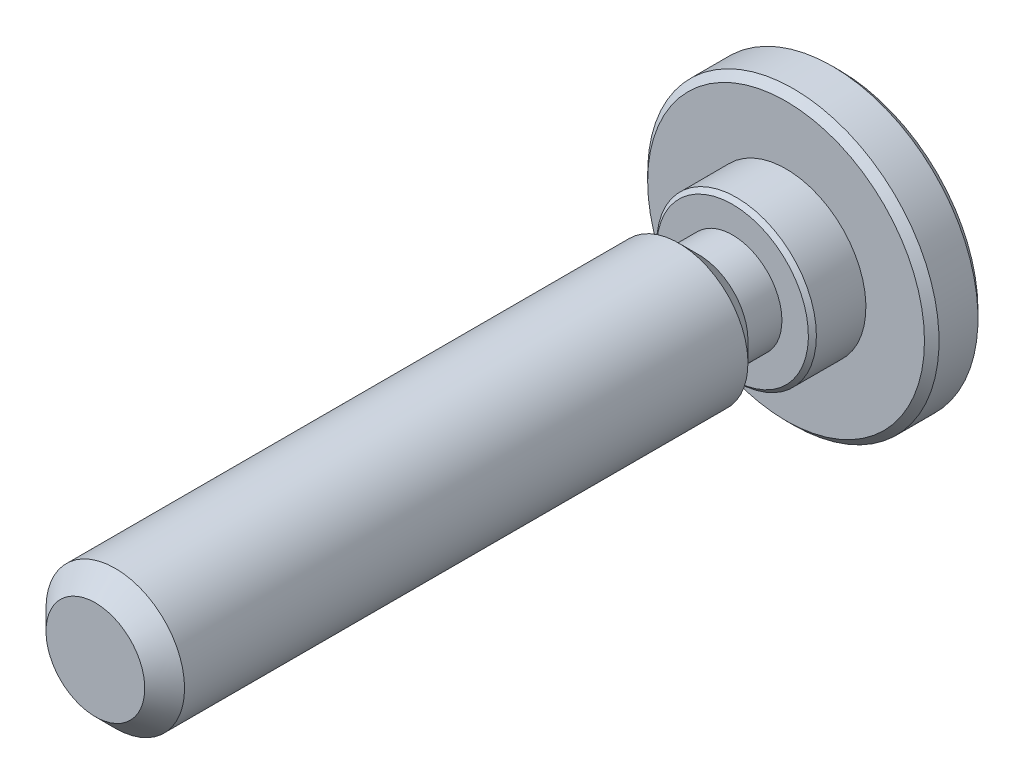
SolidWorks part; units mm, degrees
other "DetailItem1"
material "Stainless Steel (ferritic)"
ref_plane "Front Plane" through (0, 0, 0) normal (0, 0, 1) x (1, 0, 0)
ref_plane "Top Plane" through (0, 0, 0) normal (0, 1, 0) x (1, 0, 0)
ref_plane "Right Plane" through (0, 0, 0) normal (1, 0, 0) x (0, 0, -1)
sketch "Sketch1" plane through (0, 0, 0) normal (1, 0, 0) x (0, 0, -1)
  line L0 (0, 0) -> (-20.6502, 0) construction
  line L1 (0, 0) -> (1.6002, 0) construction
  line L2 (1.6002, 4.3561) -> (1.6002, -4.3561) construction
  line L3 (-20.6502, 2.0714) -> (-20.6502, -2.0714) construction
  line L4 (0, 2.3876) -> (0, -2.3876) construction
  line L5 (-20.6502, 2.0714) -> (-19.8565, 2.0714) construction
  line L6 (1.6002, 0.9922) -> (1.6002, -0.9922) construction
  line L7 (0, 2.3876) -> (-1.6002, 2.3876) construction
  line L8 (-1.6002, 2.3876) -> (-1.6002, 1.4761) construction
  line L9 (-1.6002, 1.4761) -> (-2.6162, 1.4761) construction
  line L10 (-2.6162, 1.4761) -> (-3.2115, 2.0714) construction
  point P2 (-17.8721, -2.0714)
  point P4 (-1.6002, 0)
  point P8 (1.6002, 0)
  point P11 (-20.6502, 0)
  point P14 (0, 0)
  point P19 (1.6002, 0)
  dimension "Thread Diameter" = 4.1427
  dimension "Head Diameter" = 8.7122
  dimension "Head Height" = 1.6002
  dimension "Shoulder Diameter" = 4.7752
  dimension "Shoulder Length" = 1.6002
  dimension "Thread Pitch" = 0.7937
  dimension "Drive Size" = 1.9844
  dimension "D1" = 2.7781
  dimension "D3" = 2.9521
  dimension "Undercut Length" = 1.016
  dimension "D2" = 45
  dimension "Length" = 19.05
sketch "Sketch13" plane through (0, 0, 0) normal (1, 0, 0) x (0, 0, -1)
  line L0 (1.6002, 4.3561) -> (0, 4.3561)
  line L1 (0, 4.3561) -> (0, 2.3876)
  line L3 (-20.6502, 2.0714) -> (-20.6502, 0)
  line L4 (-20.6502, 0) -> (1.6002, 0)
  line L5 (1.6002, 0) -> (1.6002, 4.3561)
  line L6 (-2.6162, 1.4761) -> (-3.2115, 2.0714) construction
  line L7 (-1.6002, 1.4761) -> (-2.6162, 1.4761) construction
  line L8 (-1.6002, 2.3876) -> (-1.6002, 1.4761) construction
  line L9 (0, 2.3876) -> (-1.6002, 2.3876) construction
  line L10 (-2.6162, 1.4761) -> (-3.2115, 2.0714)
  line L11 (-1.6002, 1.4761) -> (-2.6162, 1.4761)
  line L12 (-1.6002, 2.3876) -> (-1.6002, 1.4761)
  line L13 (0, 2.3876) -> (-1.6002, 2.3876)
  line L14 (-3.2115, 2.0714) -> (-20.6502, 2.0714)
revolve "Revolve1" add sketch "Sketch13" angle 360 about L4
sketch "Sketch2" plane through (0, 0, 20.6502) normal (0, 0, 1) x (1, 0, 0)
  circle A2 centre (0, 0) radius 2.0714
chamfer "Chamfer2" distance 0.5953 angle 45 1 edges at (0, -2.0714, 20.6502)
sketch "Sketch3" plane through (0, 0, 0) normal (1, 0, 0) x (0, 0, -1)
  line L0 (-20.6006, 2.1573) -> (-21.3943, 2.1573) construction
  line L1 (-21.3943, 2.1573) -> (-20.9975, 1.4699) construction
  line L2 (-20.9975, 1.4699) -> (-20.6006, 2.1573) construction
  line L4 (-20.6502, 2.0714) -> (-21.3447, 2.0714) construction
  line L5 (-20.9975, 2.1573) -> (-20.9975, 2.0714) construction
  line L6 (-21.3695, 2.1143) -> (-20.6254, 2.1143)
  line L7 (-20.6254, 2.1143) -> (-21.3695, 2.1143) construction
  line L8 (-20.9479, 1.5558) -> (-21.0471, 1.5558) construction
  line L9 (-20.9975, 1.5558) -> (-20.9975, 1.4699) construction
  line L10 (-20.6254, 2.1143) -> (-20.9479, 1.5558)
  line L11 (-20.9479, 1.5558) -> (-21.0471, 1.5558)
  line L12 (-21.0471, 1.5558) -> (-21.3695, 2.1143)
  point P16 (-20.9975, 2.1143)
  dimension "D1" = 0.7937
sketch "Sketch7" plane through (0, 0, -1.6002) normal (0, 0, -1) x (-1, 0, 0)
  line L1 (0, 1.1457) -> (-0.9922, 0.5728)
  line L2 (-0.9922, 0.5728) -> (-0.9922, -0.5728)
  line L3 (-0.9922, -0.5728) -> (0, -1.1457)
  line L4 (0, -1.1457) -> (0.9922, -0.5728)
  line L5 (0.9922, -0.5728) -> (0.9922, 0.5728)
  line L6 (0.9922, 0.5728) -> (0, 1.1457)
  circle A0 centre (0, 0) radius 0.9922 construction
extrude "Cut-Extrude1" cut sketch "Sketch7" against normal blind 1.4883
chamfer "Chamfer1" distance 0.2178 angle 45 2 edges at (0, -4.3561, -1.6002) (0, -4.3561, 0)
sketch "Sketch8" plane through (0, 0, -1.6002) normal (0, 0, -1) x (-1, 0, 0)
  circle A0 centre (0, 0) radius 1.1457
extrude "Cut-Extrude2" cut sketch "Sketch8" against normal through all draft 45
chamfer "Chamfer3" distance 0.1194 angle 45 1 edges at (0, -2.3876, 1.6002)
curve "Helix/Spiral1" [suppressed] pitch 0.7937 height 18.796 turns 23.68 parameters "pitch"=0.7937
sweep "Cut-Sweep1" [suppressed] cut profiles "Sketch3" path "Helix/Spiral1"
equation "\"D3@Helix/Spiral1\"=\"Length@Sketch1\"- .01"
equation "\"D1@Cut-Extrude1\" = \"Drive Size@Sketch1\" * .75"
equation "\"D1@Chamfer1\"=\"Head Diameter@Sketch1\" * .025"
equation "\"D1@Chamfer2\"=\"pitch@Helix/Spiral1\"*.750"
equation "\"D1@Sketch3\" = \"Thread Pitch@Sketch1\""
equation "\"D2@Sketch3\"=\"D1@Sketch3\"/ 1/8"
equation "\"pitch@Helix/Spiral1\" = \"Thread Pitch@Sketch1\""
equation "\"D1@Sketch1\" = \"Thread Pitch@Sketch1\" * 3.5"
equation "\"D3@Sketch1\"=\"Thread Diameter@Sketch1\" -(\"Thread Pitch@Sketch1\"*1.5)"
equation "\"D1@Chamfer3\"=\"Shoulder Diameter@Sketch1\"*.025"
